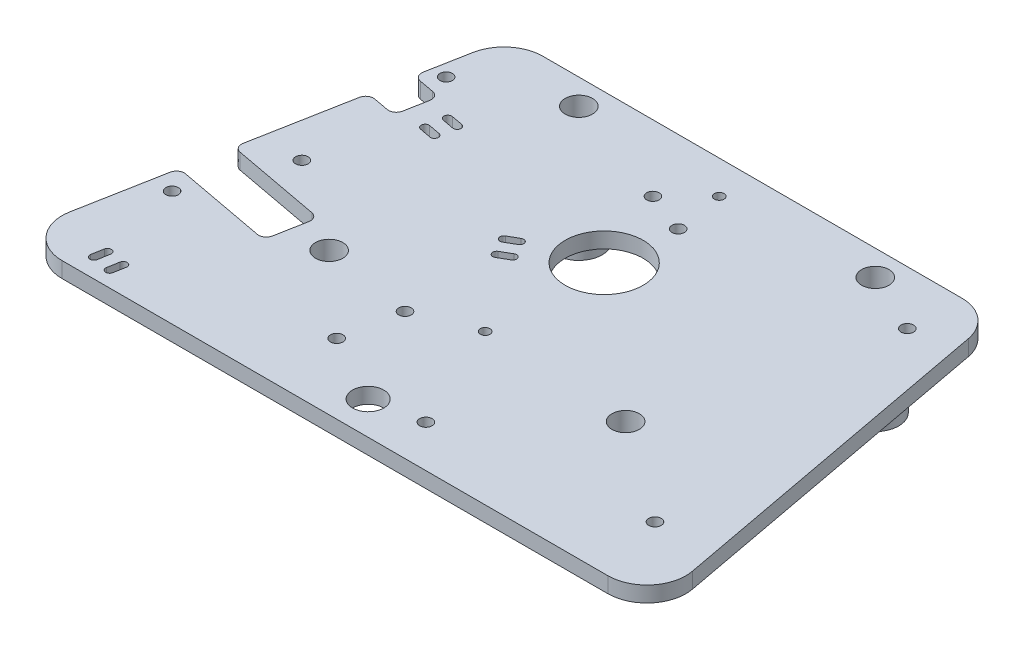
SolidWorks part; units mm, degrees
ref_plane "Plan de face" through (0, 0, 0) normal (0, 0, 1) x (1, 0, 0)
ref_plane "Plan de dessus" through (0, 0, 0) normal (0, 1, 0) x (1, 0, 0)
ref_plane "Plan de droite" through (0, 0, 0) normal (1, 0, 0) x (0, 0, -1)
sketch "Esquisse1" plane through (0, 0, 0) normal (0, 1, 0) x (1, 0, 0)
  line L0 (0, 53.5) -> (0, -53.5) construction
  line L1 (-62, 53.5) -> (62, 53.5)
  line L2 (-62, 53.5) -> (-62, -53.5)
  line L3 (-62, -53.5) -> (62, -53.5)
  line L4 (62, 53.5) -> (62, -53.5)
  dimension "D1" = 124
  dimension "D2" = 107
extrude "Boss.-Extru.1" add sketch "Esquisse1" along normal blind 4
sketch "Esquisse3" plane through (0, 0, 0) normal (0, 1, 0) x (1, 0, 0)
  line L13 (-38, -17) -> (-38, 47) construction
  line L20 (-38, 47) -> (38, 47) construction
  line L21 (38, 47) -> (38, -17) construction
  line L22 (38, -17) -> (-38, -17) construction
  line L23 (0, 47) -> (0, -16) construction
  line L24 (-38, 15) -> (38, 15) construction
  circle A1 centre (-38, -17) radius 6
  circle A7 centre (38, -17) radius 6
  circle A10 centre (38, 47) radius 6
  circle A11 centre (-38, 47) radius 6
  dimension "D6" = 12
  dimension "D9" = 12
  dimension "D10" = 12
  dimension "D13" = 12
  dimension "D2" = 17
  dimension "D3" = 38
  dimension "D4" = 38
  dimension "D5" = 17
  dimension "D7" = 47
  dimension "D8" = 47
  dimension "D11" = 38
  dimension "D12" = 38
extrude "Boss.-Extru.4" add sketch "Esquisse3" against normal blind 26
sketch "Esquisse4" plane through (0, 4, 0) normal (0, 1, 0) x (1, 0, 0)
  line L0 (0, 47) -> (0, -16) construction
  circle A0 centre (0, 15.5) radius 10
  dimension "D1" = 20
extrude "Enlèv. mat.-Extru.2" cut sketch "Esquisse4" against normal up to next
sketch "Esquisse5" plane through (0, 4, 0) normal (0, 1, 0) x (1, 0, 0)
  line L0 (-62, 53.5) -> (-82, -53.5)
  line L1 (-82, -53.5) -> (-62, -53.5)
  line L2 (-62, -53.5) -> (-62, 53.5)
  dimension "D1" = 20
extrude "Boss.-Extru.5" add sketch "Esquisse5" against normal up to surface (4 mm away) up to face at (0, 0, -5.5)
sketch "Esquisse2" plane through (0, 4, 0) normal (0, 1, 0) x (1, 0, 0)
  line L0 (-61.5, 18) -> (-8.5, 18) construction
  line L1 (-61.5, 36.5) -> (-8.5, 36.5) construction
  line L2 (-61.5, 36.5) -> (-61.5, -0.5) construction
  line L3 (-61.5, -0.5) -> (-8.5, -0.5) construction
  line L4 (-8.5, 36.5) -> (-8.5, -0.5) construction
  line L5 (-35, 36.5) -> (-35, -0.5) construction
  line L6 (-59.5, 34.5) -> (-10.5, 34.5) construction
  line L8 (-59.5, 34.5) -> (-59.5, 1.5) construction
  line L9 (-59.5, 1.5) -> (-10.5, 1.5) construction
  line L10 (-10.5, 34.5) -> (-10.5, 1.5) construction
  circle A0 centre (-61.5, 36.5) radius 1.6
  circle A3 centre (-8.5, 36.5) radius 1.6
  circle A9 centre (-61.5, -0.5) radius 1.6
  point P17 (-35, 34.5)
  point P18 (-59.5, 18)
  dimension "D5" = 3.2
  dimension "D6" = 3.2
  dimension "D7" = 3.2
  dimension "D1" = 37
  dimension "D2" = 53
  dimension "D3" = 18
  dimension "D4" = 35
  dimension "D13" = 33
  dimension "D14" = 49
extrude "Enlèv. mat.-Extru.1" cut sketch "Esquisse2" against normal through all
mirror "Symétrie1" about plane through (0, 0, 0) normal (1, 0, 0) of "Boss.-Extru.5"
sketch "Esquisse6" plane through (0, 4, 0) normal (0, 1, 0) x (1, 0, 0)
  line L0 (62, 53.5) -> (-62, 53.5) construction
  line L1 (7.253, -5.1185) -> (58.747, 2.1185) construction
  line L2 (27.7114, 36.1302) -> (38.2886, -39.1302) construction
  line L3 (33, 53.5) -> (33, -1.5) construction
  line L4 (0, 0) -> (0, 53.5) construction
  line L5 (1.9645, 32.5117) -> (53.4584, 39.7487) construction
  line L6 (53.4584, 39.7487) -> (64.0355, -35.5117) construction
  line L7 (64.0355, -35.5117) -> (12.5416, -42.7487) construction
  line L8 (12.5416, -42.7487) -> (1.9645, 32.5117) construction
  line L9 (0, 53.5) -> (33, 53.5) construction
  circle A0 centre (53.4584, 39.7487) radius 1.6
  circle A1 centre (1.9645, 32.5117) radius 1.6
  circle A2 centre (12.5416, -42.7487) radius 1.6
  circle A3 centre (64.0355, -35.5117) radius 1.6
  point P6 (33, -1.5)
  dimension "D3" = 3.2
  dimension "D4" = 3.2
  dimension "D5" = 3.2
  dimension "D6" = 3.2
  dimension "D1" = 52
  dimension "D2" = 76
  dimension "D7" = 55
  dimension "D8" = 8
  dimension "D9" = 33
extrude "Enlèv. mat.-Extru.3" cut sketch "Esquisse6" against normal through all
fillet "Congé1" radius 10 4 edges at (62, 2, -53.5) (-62, 2, -53.5) (-82, 2, 53.5) (82, 2, 53.5)
sketch "Esquisse7" plane through (0, 4, 0) normal (0, 1, 0) x (1, 0, 0)
  circle A0 centre (-38, 47) radius 3.5
  circle A1 centre (38, 47) radius 3.5
  circle A2 centre (-38, -17) radius 3.5
  circle A3 centre (38, -17) radius 3.5
  circle A4 centre (-38, 47) radius 6 construction
  circle A5 centre (38, 47) radius 6 construction
  circle A6 centre (38, -17) radius 6 construction
  circle A7 centre (-38, -17) radius 6 construction
  dimension "D1" = 7
  dimension "D2" = 7
  dimension "D3" = 7
  dimension "D4" = 7
extrude "Enlèv. mat.-Extru.4" cut sketch "Esquisse7" against normal blind 27
sketch "Esquisse8" plane through (0, -26, 0) normal (0, -1, 0) x (1, 0, 0)
  circle A0 centre (-38, -47) radius 1.7
  circle A1 centre (-38, 17) radius 1.7
  circle A2 centre (38, 17) radius 1.7
  circle A3 centre (38, -47) radius 1.7
  dimension "D1" = 3.4
extrude "Enlèv. mat.-Extru.5" cut sketch "Esquisse8" against normal through all
sketch "Esquisse9" plane through (0, 0, 0) normal (0, -1, 0) x (1, 0, 0)
  line L0 (-48.8322, 23.0041) -> (-75.3726, 18.0433)
  line L1 (-48.8322, 23.0041) -> (-46.6274, 11.2084)
  line L2 (-75.3726, 18.0433) -> (-73.1678, 6.2476)
  line L3 (-46.6274, 11.2084) -> (-73.1678, 6.2476)
  line L4 (-48.8322, 23.0041) -> (-73.1678, 6.2476) construction
  line L5 (-75.3726, 18.0433) -> (-46.6274, 11.2084) construction
  line L6 (-79.7874, 41.6627) -> (-63.5257, -45.3373) construction
  point P1 (-61, 14.6259)
  dimension "D1" = 12
  dimension "D2" = 27
  dimension "D3" = 61
extrude "Enlèv. mat.-Extru.6" cut sketch "Esquisse9" against normal up to next
fillet "Congé2" radius 2 4 edges at (-75.3726, 2, 18.0433) (-73.1678, 2, 6.2476) (-48.8322, 2, 23.0041) (-46.6274, 2, 11.2084)
sketch "Esquisse10" plane through (0, 0, 0) normal (0, 1, 0) x (1, 0, 0)
  line L0 (0, -15) -> (0, 45) construction
  circle A0 centre (0, 45) radius 3.5
  circle A1 centre (0, -15) radius 3.5
  dimension "D3" = 7
  dimension "D4" = 7
  dimension "D1" = 60
  dimension "D2" = 45
extrude "Boss.-Extru.6" add sketch "Esquisse10" against normal blind 5
sketch "Esquisse11" plane through (0, 4, 0) normal (0, 1, 0) x (1, 0, 0)
  circle A0 centre (0, 45) radius 1.25
  circle A1 centre (0, -15) radius 1.25
  circle A2 centre (0, 45) radius 3.5 construction
  circle A3 centre (0, -15) radius 3.5 construction
  dimension "D1" = 2.5
  dimension "D2" = 2.5
extrude "Enlèv. mat.-Extru.8" cut sketch "Esquisse11" against normal up to next
sketch "Esquisse12" plane through (0, 4, 0) normal (0, 1, 0) x (1, 0, 0)
  line L0 (0, 0) -> (0, -45) construction
  circle A0 centre (0, -45) radius 4
  dimension "D1" = 8
  dimension "D2" = 45
extrude "Enlèv. mat.-Extru.9" cut sketch "Esquisse12" against normal up to next
sketch "Esquisse13" plane through (0, 4, 0) normal (0, 1, 0) x (1, 0, 0)
  line L0 (-59.8708, 21.3502) -> (-67.7346, 22.8201)
  line L1 (-59.8708, 21.3502) -> (-58.0334, 31.1799)
  line L2 (-67.7346, 22.8201) -> (-65.8972, 32.6498)
  line L3 (-58.0334, 31.1799) -> (-65.8972, 32.6498)
  line L4 (-59.8708, 21.3502) -> (-65.8972, 32.6498) construction
  line L5 (-67.7346, 22.8201) -> (-58.0334, 31.1799) construction
  line L6 (-63.5257, 45.3373) -> (-72.8003, -4.2816) construction
  point P1 (-62.884, 27)
  dimension "D1" = 27
  dimension "D2" = 8
  dimension "D3" = 10
extrude "Enlèv. mat.-Extru.10" cut sketch "Esquisse13" against normal up to next
fillet "Congé3" radius 2 4 edges at (-67.7346, 2, -22.8201) (-65.8972, 2, -32.6498) (-59.8708, 2, -21.3502) (-58.0334, 2, -31.1799)
sketch "Esquisse14" plane through (0, 4, 0) normal (0, 1, 0) x (1, 0, 0)
  line L0 (-58.9521, 26.2651) -> (-51.0883, 24.7952) construction
  line L1 (-59.5033, 23.3161) -> (-58.4009, 29.214) construction
  line L2 (-51.5476, 22.3378) -> (-50.6289, 27.2526) construction
  line L3 (-49.1545, 26.977) -> (-52.1034, 27.5282) construction
  line L4 (-49.3382, 25.9941) -> (-52.2871, 26.5453)
  line L5 (-48.9708, 27.96) -> (-51.9197, 28.5112)
  line L6 (-50.0732, 22.0622) -> (-53.0221, 22.6134) construction
  line L7 (-50.2569, 21.0792) -> (-53.2058, 21.6304)
  line L8 (-49.8894, 23.0451) -> (-52.8383, 23.5963)
  arc A0 (-49.3382, 25.9941) -> (-48.9708, 27.96) centre (-49.1545, 26.977) ccw
  arc A1 (-51.9197, 28.5112) -> (-52.2871, 26.5453) centre (-52.1034, 27.5282) ccw
  arc A2 (-50.2569, 21.0792) -> (-49.8894, 23.0451) centre (-50.0732, 22.0622) ccw
  arc A3 (-52.8383, 23.5963) -> (-53.2058, 21.6304) centre (-53.0221, 22.6134) ccw
  point P8 (-50.6289, 27.2526)
  point P14 (-51.5476, 22.3378)
  dimension "D1" = 1
  dimension "D2" = 1
  dimension "D3" = 3
  dimension "D4" = 3
  dimension "D5" = 5
  dimension "D6" = 8
extrude "Enlèv. mat.-Extru.11" cut sketch "Esquisse14" against normal up to next
sketch "Esquisse15" plane through (0, 4, 0) normal (0, 1, 0) x (1, 0, 0)
  line L0 (0, 15.5) -> (-15.5885, 6.5) construction
  line L1 (0, 15.5) -> (0, 0) construction
  line L2 (-14.3385, 4.3349) -> (-16.8385, 8.6651) construction
  line L3 (-18.1375, 7.9151) -> (-15.5394, 9.4151) construction
  line L4 (-18.6375, 8.7811) -> (-16.0394, 10.2811)
  line L5 (-17.6375, 7.049) -> (-15.0394, 8.549)
  line L6 (-15.6375, 3.5849) -> (-13.0394, 5.0849) construction
  line L7 (-16.1375, 4.451) -> (-13.5394, 5.951)
  line L8 (-15.1375, 2.7189) -> (-12.5394, 4.2189)
  arc A0 (-18.6375, 8.7811) -> (-17.6375, 7.049) centre (-18.1375, 7.9151) ccw
  arc A1 (-15.0394, 8.549) -> (-16.0394, 10.2811) centre (-15.5394, 9.4151) ccw
  arc A2 (-16.1375, 4.451) -> (-15.1375, 2.7189) centre (-15.6375, 3.5849) ccw
  arc A3 (-12.5394, 4.2189) -> (-13.5394, 5.951) centre (-13.0394, 5.0849) ccw
  point P6 (-16.8385, 8.6651)
  point P15 (-14.3385, 4.3349)
  dimension "D2" = 1
  dimension "D3" = 1
  dimension "D1" = 60
  dimension "D4" = 3
  dimension "D5" = 3
  dimension "D6" = 5
  dimension "D7" = 18
extrude "Enlèv. mat.-Extru.12" cut sketch "Esquisse15" against normal up to next
sketch "Esquisse16" plane through (0, 4, 0) normal (0, 1, 0) x (1, 0, 0)
  line L0 (0, 0) -> (-7.0157, -37.5241) construction
  line L1 (-7.0157, -37.5241) -> (-71.5599, -25.4566) construction
  line L2 (-17.4967, -35.5645) -> (-14.74, -20.82) construction
  line L3 (0, 0) -> (0, -130.7909) construction
  line L4 (-71.5599, -25.4566) -> (-71.2842, -23.9822) construction
  circle A0 centre (-14.74, -20.82) radius 1.6
  circle A1 centre (-17.4967, -35.5645) radius 1.6
  circle A3 centre (0, 15.5) radius 10 construction
  circle A4 centre (-71.2842, -23.9822) radius 1.6
  dimension "D3" = 3.2
  dimension "D4" = 3.2
  dimension "D5" = 3.2
  dimension "D7" = 36.32
  dimension "D1" = 15
  dimension "D2" = 55
  dimension "D6" = 14.74
  dimension "D8" = 10.59
  dimension "D9" = 1.5
extrude "Enlèv. mat.-Extru.13" cut sketch "Esquisse16" against normal up to next
sketch "Esquisse17" plane through (0, 4, 0) normal (0, 1, 0) x (1, 0, 0)
  line L0 (-65, -53.5) -> (-63.9581, -47.5912) construction
  line L1 (-69.9577, -53.5) -> (69.9577, -53.5) construction
  line L2 (-66.4201, -47.157) -> (-61.4961, -48.0253) construction
  line L3 (-66.6806, -48.6342) -> (-66.1597, -45.6798) construction
  line L4 (-67.6654, -48.4606) -> (-67.1445, -45.5062)
  line L5 (-65.6958, -48.8079) -> (-65.1749, -45.8535)
  line L6 (-61.2356, -46.5481) -> (-61.7566, -49.5025) construction
  line L7 (-60.2508, -46.7217) -> (-60.7718, -49.6761)
  line L8 (-62.2204, -46.3744) -> (-62.7414, -49.3288)
  arc A0 (-67.6654, -48.4606) -> (-65.6958, -48.8079) centre (-66.6806, -48.6342) ccw
  arc A1 (-65.1749, -45.8535) -> (-67.1445, -45.5062) centre (-66.1597, -45.6798) ccw
  arc A2 (-60.2508, -46.7217) -> (-62.2204, -46.3744) centre (-61.2356, -46.5481) ccw
  arc A3 (-62.7414, -49.3288) -> (-60.7718, -49.6761) centre (-61.7566, -49.5025) ccw
  point P8 (-66.4201, -47.157)
  point P14 (-61.4961, -48.0253)
  dimension "D1" = 1
  dimension "D2" = 1
  dimension "D3" = 3
  dimension "D4" = 3
  dimension "D5" = 5
  dimension "D6" = 65
  dimension "D7" = 6
  dimension "D8" = 80
extrude "Enlèv. mat.-Extru.14" cut sketch "Esquisse17" against normal up to next
